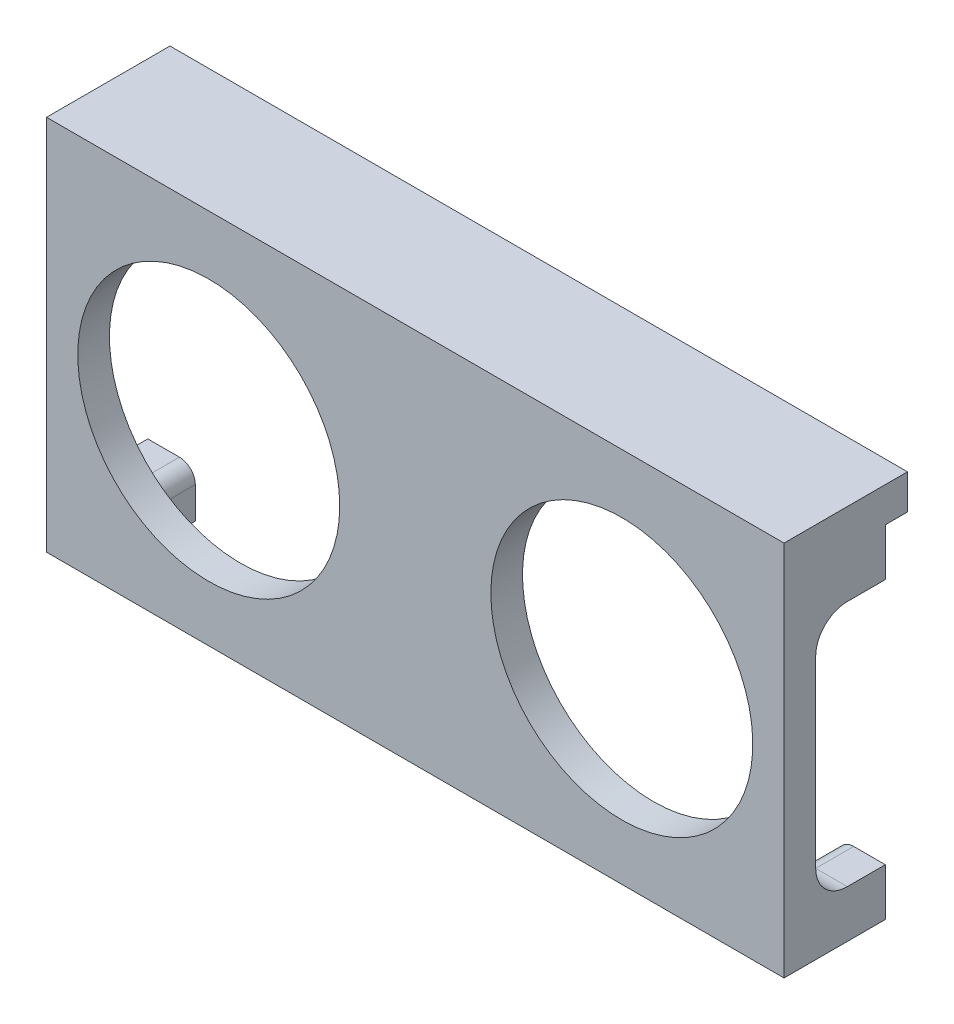
SolidWorks part; units mm, degrees
ref_plane "Front Plane" through (0, 0, 0) normal (0, 0, 1) x (1, 0, 0)
ref_plane "Top Plane" through (0, 0, 0) normal (0, 1, 0) x (1, 0, 0)
ref_plane "Right Plane" through (0, 0, 0) normal (1, 0, 0) x (0, 0, -1)
sketch "Sketch1" plane through (0, 0, 0) normal (0, 0, 1) x (1, 0, 0)
  line L3 (23.5, 13) -> (-23.5, 13) construction
  line L4 (23.3, 13) -> (-23.3, 13)
  line L6 (-23.3, 13) -> (-23.3, -10.8)
  line L7 (-23.3, -10.8) -> (23.3, -10.8)
  line L8 (23.3, -10.8) -> (23.3, 13)
  line L9 (-23.3, 13) -> (-23.3, -10.8)
  line L10 (-23.3, -10.8) -> (23.3, -10.8)
  line L11 (23.3, -10.8) -> (23.3, 13)
  dimension "D1" = 0.2
extrude "Boss-Extrude1" add sketch "Sketch1" against normal blind 2
sketch "Sketch2" plane through (0, 0, -2) normal (0, 0, -1) x (-1, 0, 0)
  line L0 (0, 13) -> (0, -10.8) construction
  line L1 (-23.3, 13) -> (23.3, 13) construction
  line L2 (23.3, -10.8) -> (-23.3, -10.8) construction
  line L3 (0, 0) -> (23.3, 0) construction
  line L5 (23.3, 13) -> (23.3, -10.8) construction
  line L6 (20.3, 10.8) -> (20.3, 7.8)
  line L7 (23.3, -10.8) -> (20.3, -10.8)
  line L8 (23.3, -10.8) -> (23.3, -7.8)
  line L9 (23.3, -7.8) -> (20.3, -7.8)
  line L10 (20.3, -10.8) -> (20.3, -7.8)
  line L11 (23.3, 7.8) -> (20.3, 7.8)
  line L12 (23.3, 10.8) -> (23.3, 7.8)
  line L13 (23.3, 10.8) -> (20.3, 10.8)
  line L14 (-20.3, -10.8) -> (-20.3, -7.8)
  line L15 (-23.3, -7.8) -> (-20.3, -7.8)
  line L16 (-23.3, -10.8) -> (-23.3, -7.8)
  line L17 (-23.3, -10.8) -> (-20.3, -10.8)
  line L18 (-23.3, 10.8) -> (-20.3, 10.8)
  line L19 (-23.3, 10.8) -> (-23.3, 7.8)
  line L20 (-23.3, 7.8) -> (-20.3, 7.8)
  line L21 (-20.3, 10.8) -> (-20.3, 7.8)
  dimension "D1" = 3
  dimension "D2" = 3
extrude "Boss-Extrude2" add sketch "Sketch2" along normal blind 4.4
sketch "Sketch3" plane through (0, 0, -2) normal (0, 0, -1) x (-1, 0, 0)
  line L1 (-23.3, 13) -> (23.3, 13)
  line L2 (-23.3, 13) -> (-23.3, 10.8)
  line L3 (-23.3, 10.8) -> (23.3, 10.8)
  line L4 (23.3, 13) -> (23.3, 10.8)
extrude "Boss-Extrude3" add sketch "Sketch3" along normal blind 5.8
fillet "Fillet2" radius 1 6 edges at (20.3, -7.8, -4.2) (-20.3, -7.8, -4.2) (-20.3, 7.8, -4.2) (-20.3, 10.8, -4.2) (20.3, 7.8, -4.2) (20.3, 10.8, -4.2)
fillet "Fillet3" radius 2 15 edges at (-20.5929, -8.0929, -2) (22.3, -7.8, -2) (20.5929, -8.0929, -2) (22.3, 7.8, -2) (20.5929, 8.0929, -2) (20.3, 9.3, -2) (20.0071, 10.5071, -2) (-22.3, 7.8, -2) (-20.5929, 8.0929, -2) (-20.3, 9.3, -2) (-20.0071, 10.5071, -2) (20.3, -9.8, -2) (0, 10.8, -2)
sketch "Sketch4" plane through (0, 0, 0) normal (0, 0, 1) x (1, 0, 0)
  line L0 (-23.5, -11) -> (23.5, -11) construction
  line L1 (-23.5, -11) -> (23.5, -11) construction
  line L2 (-23.5, 13) -> (-23.5, -11) construction
  line L3 (23.5, -11) -> (23.5, 13) construction
  line L4 (-23.5, 13) -> (-23.5, -11) construction
  line L5 (23.5, -11) -> (23.5, 13) construction
  line L6 (-23.5, 1) -> (23.5, 1) construction
  line L8 (23.3, 13) -> (-23.3, 13) construction
  line L9 (0, 13) -> (0, 0) construction
  circle A0 centre (-13.05, 1) radius 8.2756
  circle A1 centre (13.05, 1) radius 8.2756
  dimension "D1" = 13.05
extrude "Cut-Extrude1" cut sketch "Sketch4" against normal up to next
